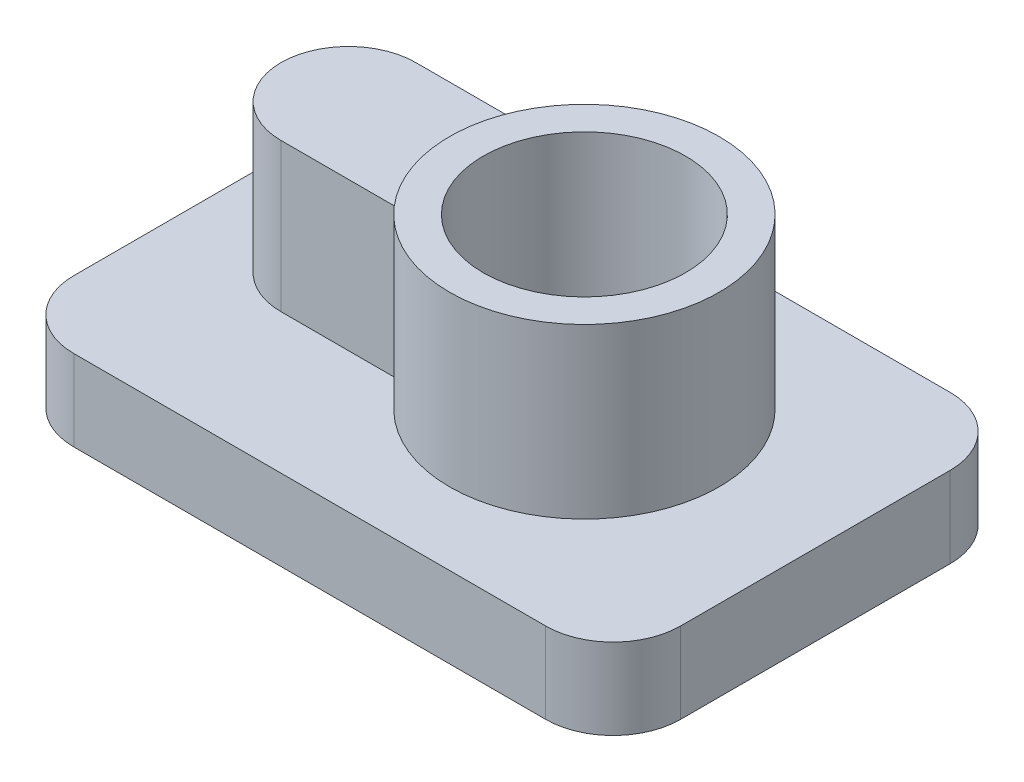
SolidWorks part; units mm, degrees
ref_plane "Plano frontal" through (0, 0, 0) normal (0, 0, 1) x (1, 0, 0)
ref_plane "Plano superior" through (0, 0, 0) normal (0, 1, 0) x (1, 0, 0)
ref_plane "Plano direito" through (0, 0, 0) normal (1, 0, 0) x (0, 0, -1)
sketch "Esboço1" plane through (0, 0, 0) normal (0, 0, 1) x (1, 0, 0)
  line L0 (0, 0) -> (90, 0)
  line L1 (90, 0) -> (90, 12)
  line L2 (90, 12) -> (0, 12)
  line L3 (0, 12) -> (0, 0)
  dimension "D1" = 12
  dimension "D2" = 90
extrude "Ressalto-extrusão1" add sketch "Esboço1" along normal blind 60
fillet "Filete2" radius 10 1 edges at (0, 6, 60)
fillet "Filete3" radius 10 1 edges at (0, 6, 0)
fillet "Filete4" radius 10 2 edges at (90, 6, 0) (90, 6, 60)
sketch "Esboço5" plane through (0, 12, 0) normal (0, 1, 0) x (1, 0, 0)
  line L0 (90, -50) -> (90, -10) construction
  circle A1 centre (55, -29.262) radius 20
  dimension "D1" = 40
  dimension "D2" = 35
extrude "Ressalto-extrusão3" add sketch "Esboço5" along normal blind 25
sketch "Esboço8" plane through (0, 12, 0) normal (0, 1, 0) x (1, 0, 0)
  line L0 (55, -29.262) -> (20, -29.262) construction
  line L1 (55, -39.262) -> (20, -39.262)
  line L2 (55, -19.262) -> (20, -19.262)
  arc A0 (55, -39.262) -> (55, -19.262) centre (55, -29.262) ccw
  arc A1 (20, -19.262) -> (20, -39.262) centre (20, -29.262) ccw
  point P3 (37.5, -29.262)
  dimension "D1" = 35
  dimension "D2" = 20
extrude "Ressalto-extrusão4" add sketch "Esboço8" along normal blind 22
sketch "Esboço9" plane through (0, 37, 0) normal (0, 1, 0) x (1, 0, 0)
  circle A0 centre (55, -29.262) radius 15
  dimension "D1" = 30
extrude "Corte-extrusão1" cut sketch "Esboço9" against normal blind 37
